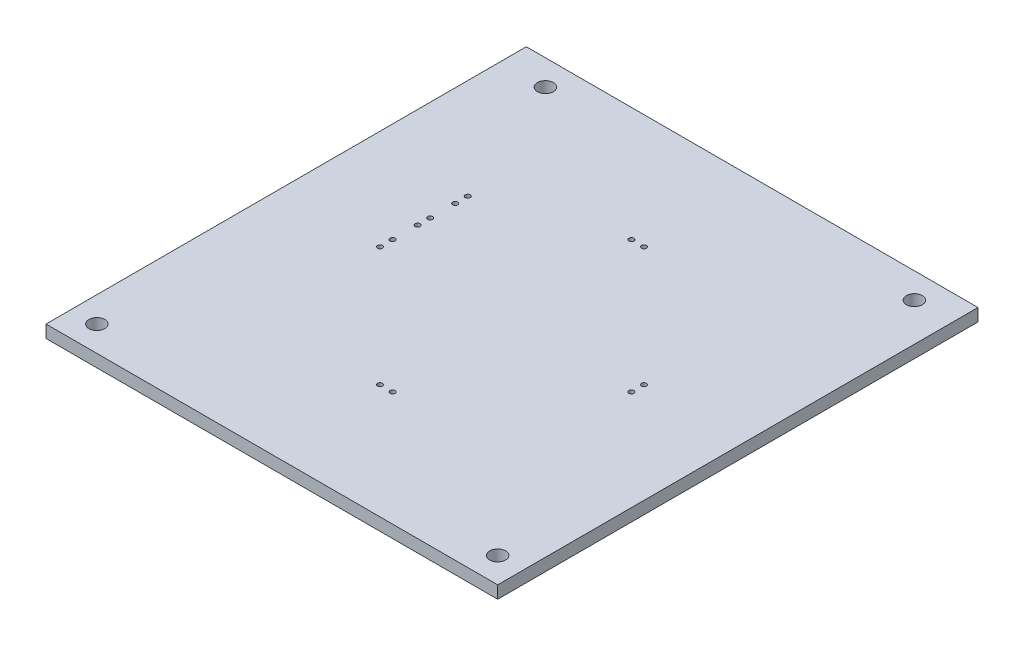
SolidWorks part; units mm, degrees
ref_plane "Front" through (0, 0, 0) normal (0, 0, 1) x (1, 0, 0)
ref_plane "Top" through (0, 0, 0) normal (0, 1, 0) x (1, 0, 0)
ref_plane "Right" through (0, 0, 0) normal (1, 0, 0) x (0, 0, -1)
sketch "Sketch1" plane through (0, 0, 0) normal (0, 1, 0) x (1, 0, 0)
  line L1 (-45.085, -47.9425) -> (45.085, -47.9425)
  line L2 (-45.085, -47.9425) -> (-45.085, 47.9425)
  line L3 (-45.085, 47.9425) -> (45.085, 47.9425)
  line L4 (45.085, -47.9425) -> (45.085, 47.9425)
  line L5 (-45.085, -47.9425) -> (45.085, 47.9425) construction
  line L6 (-45.085, 47.9425) -> (45.085, -47.9425) construction
  point P0 (0, 0)
  dimension "D1" = 95.885
  dimension "D2" = 90.17
extrude "Boss-Extrude1" add sketch "Sketch1" along normal blind 2.5
sketch "Sketch2" plane through (0, 2.5, 0) normal (0, 1, 0) x (1, 0, 0)
  line L0 (-45.085, 47.9425) -> (-45.085, -47.9425) construction
  line L1 (-45.085, -47.9425) -> (45.085, -47.9425) construction
  circle A0 centre (-40.005, -42.8625) radius 1.5875
  circle A1 centre (-36.195, 42.8625) radius 1.5875
  circle A2 centre (37.465, 42.8625) radius 1.5875
  circle A3 centre (40.005, -42.8625) radius 1.5875
  dimension "D1" = 3.175
  dimension "D2" = 5.08
  dimension "D3" = 5.08
  dimension "D4" = 80.01
  dimension "D5" = 85.725
  dimension "D6" = 3.81
  dimension "D7" = 73.66
extrude "Cut-Extrude1" cut sketch "Sketch2" against normal blind 2.5
sketch "Sketch3" plane through (0, 2.5, 0) normal (0, 1, 0) x (1, 0, 0)
  line L0 (-45.085, 47.9425) -> (-45.085, -47.9425) construction
  circle A0 centre (-25.085, 1.25) radius 0.5
  circle A1 centre (-25.085, -1.25) radius 0.5
  dimension "D1" = 1
  dimension "D2" = 1.25
  dimension "D3" = 2.5
  dimension "D4" = 20
extrude "Cut-Extrude2" cut sketch "Sketch3" against normal blind 10
ref_axis "Axis1" through (0, 50, 0) along (0, -1, 0)
pattern_circular "CirPattern1" count 4 over 360 about axis through (0, 50, 0) along (0, -1, 0) of "Cut-Extrude2"
pattern_linear "LPattern1" count 3 spacing 7.5 along (0, 0, -1) of "Cut-Extrude2"
